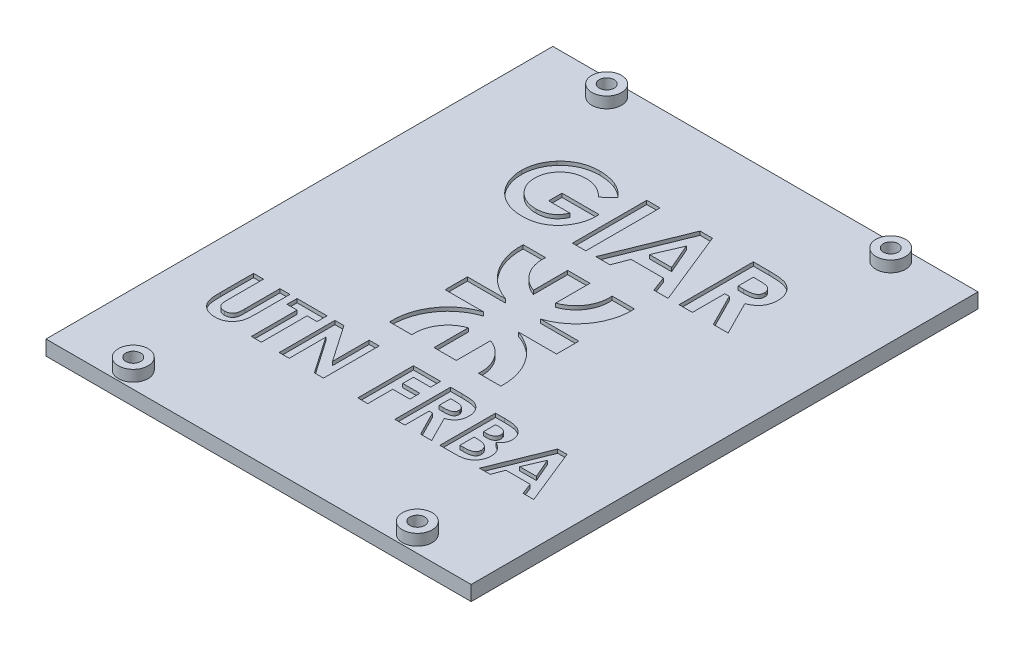
SolidWorks part; units mm, degrees
material "PLA_Tapa"
ref_plane "Front Plane" through (0, 0, 0) normal (0, 0, 1) x (1, 0, 0)
ref_plane "Top Plane" through (0, 0, 0) normal (0, 1, 0) x (1, 0, 0)
ref_plane "Right Plane" through (0, 0, 0) normal (1, 0, 0) x (0, 0, -1)
sketch "Sketch2" plane through (0, 0, 0) normal (0, 1, 0) x (1, 0, 0)
  line L0 (0, 0) -> (0, -50000) construction
  line L1 (-57.25, 68.25) -> (57.25, 68.25)
  line L2 (-57.25, 68.25) -> (-57.25, -68.25)
  line L3 (-57.25, -68.25) -> (57.25, -68.25)
  line L4 (57.25, 68.25) -> (57.25, -68.25)
  line L5 (-57.25, 68.25) -> (57.25, -68.25) construction
  line L6 (-57.25, -68.25) -> (57.25, 68.25) construction
  line L7 (0, 0) -> (50000, 0) construction
  circle A0 centre (-38.25, 63.75) radius 2
  circle A1 centre (-38.25, -63.75) radius 2
  circle A2 centre (38.25, -63.75) radius 2
  circle A3 centre (38.25, 63.75) radius 2
  point P0 (0, 0)
  dimension "D3" = 4
  dimension "D4" = 38.25
  dimension "D5" = 63.75
  dimension "D1" = 114.5
  dimension "D2" = 136.5
extrude "Boss-Extrude1" add sketch "Sketch2" along normal blind 4
sketch "Sketch3" plane through (0, 4, 0) normal (0, 1, 0) x (1, 0, 0)
  line L0 (-57.25, 25) -> (57.25, 25) construction
  line L1 (-9, 18) -> (-9, -18) construction
  line L2 (-15, 18) -> (15, 18) construction
  line L3 (-57.25, -45) -> (57.25, -45) construction
  line L4 (-47.25, 25) -> (57.25, 25) construction
  line L5 (-57.25, 68.25) -> (-57.25, -68.25) construction
  line L6 (57.25, -68.25) -> (57.25, 68.25) construction
  line L7 (-47.25, -45) -> (57.25, -45) construction
  line L8 (-57.25, -45) -> (-57.25, -68.25) construction
  line L9 (-57.25, -45) -> (-57.25, -25) construction
  line L10 (-57.25, -25) -> (-57.25, 25) construction
  line L11 (-57.25, 25) -> (-57.25, 45) construction
  line L12 (-57.25, 45) -> (-57.25, 68.25) construction
  line L13 (294.0315, 252.5659) -> (1544.0315, 252.5659) construction
  line L14 (-15, 18) -> (-15, -18) construction
  line L15 (-15, -18) -> (15, -18) construction
  line L16 (15, 18) -> (15, -18) construction
  line L17 (-15, 18) -> (15, -18) construction
  line L18 (-15, -18) -> (15, 18) construction
  line L19 (-3, 18) -> (-3, 8.7647) construction
  line L20 (3, 18) -> (3, 8.7647) construction
  line L21 (9, 18) -> (9, -18) construction
  line L22 (-15, 12) -> (15, 12) construction
  line L23 (-15, 6) -> (15, 6) construction
  line L24 (-15, 0) -> (15, 0) construction
  line L25 (-15, -6) -> (15, -6) construction
  line L26 (-15, -12) -> (15, -12) construction
  line L27 (-15, -3) -> (-4.6837, -3)
  line L28 (-15, 3) -> (-4.6837, 3)
  line L29 (-3, 18) -> (3, 18)
  line L30 (3, 18) -> (3, 8.7647)
  line L31 (3, -18) -> (-3, -18)
  line L32 (-3, -18) -> (-3, -8.7647)
  line L33 (-15, 3) -> (-15, -3)
  line L34 (15, 3) -> (15, -3)
  line L35 (0, -18) -> (0, -17.25) construction
  line L36 (-3, -8.7647) -> (-3, -18) construction
  line L37 (-3, 18) -> (-3, -18) construction
  line L38 (-4.6837, 3) -> (4.6837, 3) construction
  line L39 (3, -8.7647) -> (3, -18) construction
  line L40 (3, 18) -> (3, -18) construction
  line L41 (3, -8.7647) -> (3, -18)
  line L42 (4.6837, -3) -> (15, -3)
  line L43 (-15, -3) -> (15, -3) construction
  line L44 (-14.9812, -18) -> (-8.9687, -18)
  line L45 (8.9687, -18) -> (14.9812, -18)
  line L46 (0, 18) -> (0, 17.25)
  line L47 (-8.9687, 18) -> (-14.9812, 18)
  line L48 (-3, 8.7647) -> (-3, 18)
  line L49 (8.9687, 18) -> (14.9812, 18)
  line L52 (-15, 3) -> (15, 3) construction
  line L53 (4.6837, 3) -> (15, 3)
  arc A8 (14.9812, -18) -> (4.6837, -3) centre (0, -17.25) ccw
  arc A9 (8.9687, -18) -> (3, -8.7647) centre (0, -17.25) ccw
  arc A10 (-3, -8.7647) -> (-8.9687, -18) centre (0, -17.25) ccw
  arc A11 (-4.6837, -3) -> (-14.9812, -18) centre (0, -17.25) ccw
  arc A12 (-14.9812, 18) -> (-4.6837, 3) centre (0, 17.25) ccw
  arc A13 (-8.9687, 18) -> (-3, 8.7647) centre (0, 17.25) ccw
  arc A14 (3, 8.7647) -> (8.9687, 18) centre (0, 17.25) ccw
  arc A15 (4.6837, 3) -> (14.9812, 18) centre (0, 17.25) ccw
  text T0 "GIAR" font "Century Gothic" height 20
  text T1 "UTN FRBA" font "Century Gothic" height 20
  dimension "D3" = 50
  dimension "D6" = 6
  dimension "D15" = 3
  dimension "D17" = 0.75
  dimension "D18" = 0.75
  dimension "D1" = 20
  dimension "D2" = 20
  dimension "D4" = 36
  dimension "D5" = 30
  dimension "D7" = 6
  dimension "D8" = 6
  dimension "D9" = 6
  dimension "D10" = 6
  dimension "D11" = 6
  dimension "D12" = 6
  dimension "D13" = 6
  dimension "D14" = 6
  dimension "D16" = 3
extrude "Cut-Extrude1" cut sketch "Sketch3" against normal blind 1 contours L53 A15 L49 A14 L30 L29 L48 A13 L47 A12 L28 L33 L27 A11 L44 A10 L32 L31 L41 A9 L45 A8 L42 L34 region at (0, 4, 0)
sketch "Sketch4" plane through (0, 4, 4) normal (0, 1, 0) x (1, 0, 0)
  line L0 (-57.25, 29) -> (57.25, 29) construction
  line L3 (-57.25, -36) -> (57.25, -36) construction
  line L4 (-47.25, 29) -> (57.25, 29) construction
  line L5 (-8.9687, 22) -> (-14.9812, 22) construction
  line L6 (-14.9812, -14) -> (-8.9687, -14) construction
  line L7 (-47.25, -36) -> (57.25, -36) construction
  line L8 (-57.25, 72.25) -> (-57.25, -64.25) construction
  line L9 (-57.25, -36) -> (-57.25, -21) construction
  line L10 (-57.25, -21) -> (-57.25, 29) construction
  line L11 (-57.25, 29) -> (-57.25, 49) construction
  line L13 (294.0315, 252.5659) -> (1544.0315, 252.5659) construction
  line L17 (57.25, -64.25) -> (57.25, 72.25) construction
  text T0 "GIAR" font "Century Gothic" height 20
  text T1 "UTN FRBA" font "Century Gothic" height 15
  dimension "D3" = 7
  dimension "D1" = 15
  dimension "D2" = 20
  dimension "D4" = 7
extrude "Cut-Extrude2" cut sketch "Sketch4" against normal blind 1
sketch "Sketch5" plane through (0, 4, 0) normal (0, 1, 0) x (1, 0, 0)
  circle A0 centre (38.25, -63.75) radius 2 construction
  circle A1 centre (-38.25, -63.75) radius 2 construction
  circle A2 centre (38.25, 63.75) radius 2 construction
  circle A3 centre (-38.25, 63.75) radius 2 construction
  circle A12 centre (38.25, -63.75) radius 2
  circle A13 centre (-38.25, -63.75) radius 2
  circle A14 centre (38.25, 63.75) radius 2
  circle A15 centre (-38.25, 63.75) radius 2
  circle A16 centre (38.25, -63.75) radius 4
  circle A17 centre (-38.25, -63.75) radius 4
  circle A18 centre (38.25, 63.75) radius 4
  circle A19 centre (-38.25, 63.75) radius 4
  dimension "D1" = 2
extrude "Boss-Extrude2" add sketch "Sketch5" along normal blind 3
sketch "Sketch6" plane through (0, 0, 0) normal (0, -1, 0) x (1, 0, 0)
  line L0 (-6.28, -13.7458) -> (-6.28, -30.4099) construction
  line L1 (-2.28, 37.0901) -> (-57.25, 37.0901) construction
  line L2 (-52.75, -30.4099) -> (-6.28, -30.4099) construction
  line L3 (57.25, -68.25) -> (-57.25, -68.25) construction
  line L4 (-6.28, 33.0901) -> (-52.75, 33.0901) construction
  line L5 (-6.28, 33.0901) -> (-6.28, 8.7362) construction
  line L6 (-57.25, -68.25) -> (-57.25, 68.25) construction
  line L7 (14.1361, 8.7362) -> (14.1361, -13.7458) construction
  line L8 (14.1361, -13.7458) -> (-6.28, -13.7458) construction
  line L9 (14.1361, 8.7362) -> (-6.28, 8.7362) construction
  line L10 (-52.75, -34.4099) -> (-6.28, -34.4099)
  line L11 (-2.28, -21.7458) -> (-2.28, -30.4099)
  line L12 (14.1361, -17.7458) -> (1.72, -17.7458)
  line L13 (18.1361, 8.7362) -> (18.1361, -13.7457)
  line L14 (14.1361, 12.7362) -> (1.72, 12.7362)
  line L15 (-2.28, 33.0901) -> (-2.28, 16.7362)
  line L16 (-6.28, 37.0901) -> (-52.75, 37.0901)
  line L17 (-2.28, 37.0901) -> (-2.28, 12.7362) construction
  line L18 (18.1361, 12.7362) -> (-2.28, 12.7362) construction
  line L19 (18.1361, 12.7362) -> (18.1361, -17.7458) construction
  line L20 (18.1361, -17.7458) -> (-2.28, -17.7458) construction
  line L21 (-2.28, -17.7458) -> (-2.28, -34.4099) construction
  line L22 (-57.25, -34.4099) -> (-2.28, -34.4099) construction
  line L23 (-52.75, -34.4099) -> (-52.75, 37.0901)
  line L24 (-6.28, 33.0901) -> (-57.25, 33.0901) construction
  line L25 (-57.25, -30.4099) -> (-6.28, -30.4099) construction
  arc A0 (-6.28, 37.0901) -> (-2.28, 33.0901) centre (-6.28, 33.0901) cw
  arc A1 (-2.28, 16.7362) -> (1.72, 12.7362) centre (1.72, 16.7362) ccw
  arc A2 (14.1361, 12.7362) -> (18.1361, 8.7362) centre (14.1361, 8.7362) cw
  arc A3 (18.1361, -13.7457) -> (14.1361, -17.7458) centre (14.1361, -13.7458) cw
  arc A4 (1.72, -17.7458) -> (-2.28, -21.7458) centre (1.72, -21.7458) ccw
  arc A5 (-2.28, -30.4099) -> (-6.28, -34.4099) centre (-6.28, -30.4099) cw
  dimension "D8" = 4
  dimension "D1" = 4
  dimension "D2" = 37.8401
  dimension "D3" = 63.5
  dimension "D4" = 50.97
  dimension "D5" = 71.3861
  dimension "D6" = 16.6642
  dimension "D7" = 24.3538
  dimension "D9" = 4.5
extrude "Cut-Extrude3" cut sketch "Sketch6" against normal blind 1.5 and the other way through all
chamfer "Chamfer1" distance 1.5 angle 45 14 edges at (-29.515, 0, -34.4099) (-3.4516, 0, -33.2384) (-2.28, 0, -26.0778) (-1.1084, 0, -18.9173) (7.9281, 0, -17.7458) (16.9645, 0, -16.5742) (18.1361, 0, -2.5048) (16.9645, 0, 11.5647) (7.928, 0, 12.7362) (-1.1084, 0, 13.9078) (-2.28, 0, 24.9131) (-3.4516, 0, 35.9185) (-52.75, 0, 1.3401) (-29.515, 0, 37.0901)
